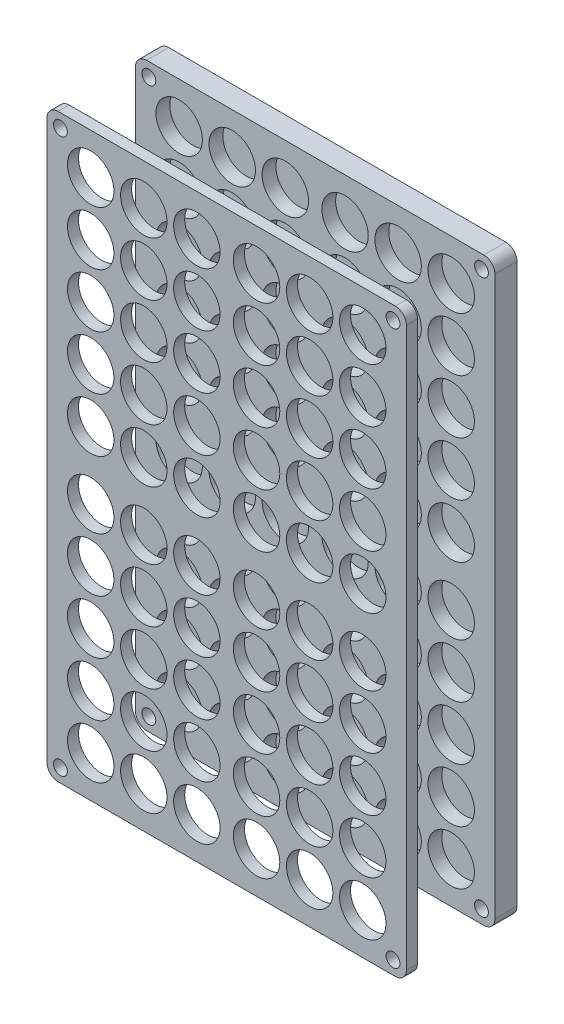
SolidWorks part; units mm, degrees
other "Top Media Holder"
ref_plane "Front Plane" through (0, 0, 0) normal (1, 0, 0) x (0, 1, 0)
ref_plane "Top Plane" through (0, 0, 0) normal (0, 0, 1) x (0, 1, 0)
ref_plane "Right Plane" through (0, 0, 0) normal (0, 1, 0) x (-1, 0, 0)
sketch "Sketch1" plane through (0, 0, 0) normal (0, 0, 1) x (0, 1, 0)
  line L1 (-105, -65) -> (105, -65)
  line L2 (-105, -65) -> (-105, 65)
  line L3 (-105, 65) -> (105, 65)
  line L4 (105, -65) -> (105, 65)
  line L5 (-105, -65) -> (105, 65) construction
  line L6 (-105, 65) -> (105, -65) construction
  point P0 (0, 0)
  dimension "D1" = 130
  dimension "D2" = 210
extrude "120 x 200 x 67 th" add sketch "Sketch1" along normal blind 40
sketch "Sketch2" plane through (0, 0, 40) normal (0, 0, 1) x (1, 0, 0)
  line L0 (-65, 0) -> (65, 0) construction
  line L1 (-65, 105) -> (-65, -105) construction
  line L2 (65, -105) -> (65, 105) construction
  line L3 (0, 105) -> (0, -105) construction
  line L4 (65, 105) -> (-65, 105) construction
  line L5 (-65, -105) -> (65, -105) construction
  line L9 (-65, 40) -> (65, 40) construction
  line L11 (-62.6582, -100.1582) -> (-65, -100.1582)
  line L12 (-60.1582, -102.6582) -> (-60.1582, -105)
  circle A2 centre (-49.2, -12.1416) radius 8.4
  circle A32 centre (-30, -12.1416) radius 8.4
  circle A33 centre (-10.8, -12.1416) radius 8.4
  circle A34 centre (10.8, -12.1416) radius 8.4
  circle A35 centre (30, -12.1416) radius 8.4
  circle A36 centre (49.2, -12.1416) radius 8.4
  circle A37 centre (10.8, -31.6416) radius 8.4
  circle A38 centre (30, -31.6416) radius 8.4
  circle A39 centre (49.2, -31.6416) radius 8.4
  circle A40 centre (-10.8, -31.6416) radius 8.4
  circle A41 centre (-30, -31.6416) radius 8.4
  circle A42 centre (-49.2, -31.6416) radius 8.4
  circle A43 centre (10.8, -51.1416) radius 8.4
  circle A44 centre (30, -51.1416) radius 8.4
  circle A45 centre (49.2, -51.1416) radius 8.4
  circle A46 centre (-10.8, -51.1416) radius 8.4
  circle A47 centre (-30, -51.1416) radius 8.4
  circle A48 centre (-49.2, -51.1416) radius 8.4
  circle A49 centre (10.8, -70.6416) radius 8.4
  circle A50 centre (30, -70.6416) radius 8.4
  circle A51 centre (49.2, -70.6416) radius 8.4
  circle A52 centre (-10.8, -70.6416) radius 8.4
  circle A53 centre (-30, -70.6416) radius 8.4
  circle A54 centre (-49.2, -70.6416) radius 8.4
  circle A55 centre (10.8, -90.1416) radius 8.4
  circle A56 centre (30, -90.1416) radius 8.4
  circle A57 centre (49.2, -90.1416) radius 8.4
  circle A58 centre (-10.8, -90.1416) radius 8.4
  circle A59 centre (-30, -90.1416) radius 8.4
  circle A60 centre (-49.2, -90.1416) radius 8.4
  circle A66 centre (-60.1582, -100.1582) radius 2.5
  circle A67 centre (-60.1582, 100.1582) radius 2.5
  circle A68 centre (60.1582, -100.1582) radius 2.5
  circle A69 centre (60.1582, 100.1582) radius 2.5
  circle A70 centre (-49.2, 90.1416) radius 8.4
  circle A71 centre (-30, 90.1416) radius 8.4
  circle A72 centre (-10.8, 90.1416) radius 8.4
  circle A73 centre (49.2, 90.1416) radius 8.4
  circle A74 centre (30, 90.1416) radius 8.4
  circle A75 centre (10.8, 90.1416) radius 8.4
  circle A76 centre (-49.2, 70.6416) radius 8.4
  circle A77 centre (-30, 70.6416) radius 8.4
  circle A78 centre (-10.8, 70.6416) radius 8.4
  circle A79 centre (49.2, 70.6416) radius 8.4
  circle A80 centre (30, 70.6416) radius 8.4
  circle A81 centre (10.8, 70.6416) radius 8.4
  circle A82 centre (-49.2, 51.1416) radius 8.4
  circle A83 centre (-30, 51.1416) radius 8.4
  circle A84 centre (-10.8, 51.1416) radius 8.4
  circle A85 centre (49.2, 51.1416) radius 8.4
  circle A86 centre (30, 51.1416) radius 8.4
  circle A87 centre (10.8, 51.1416) radius 8.4
  circle A88 centre (-49.2, 31.6416) radius 8.4
  circle A89 centre (-30, 31.6416) radius 8.4
  circle A90 centre (-10.8, 31.6416) radius 8.4
  circle A91 centre (49.2, 31.6416) radius 8.4
  circle A92 centre (30, 31.6416) radius 8.4
  circle A93 centre (10.8, 31.6416) radius 8.4
  circle A94 centre (30, 12.1416) radius 8.4
  circle A95 centre (10.8, 12.1416) radius 8.4
  circle A96 centre (-10.8, 12.1416) radius 8.4
  circle A97 centre (-30, 12.1416) radius 8.4
  circle A98 centre (-49.2, 12.1416) radius 8.4
  circle A99 centre (49.2, 12.1416) radius 8.4
  point P35 (-32.5, 53)
  dimension "D2" = 3
  dimension "D4" = 5
  dimension "D3" = 5
extrude "16.8 D and 52 D tube holes" cut sketch "Sketch2" against normal blind 37 contours A32 | A33 | A34 | A35 | A36 | A42 | A41 | A40 | A37 | A38 | A39 | A48 | A47 | A46 | A43 | A44 | A45 | A54 | A53 | A52 | A49 | A50 | A51 | A60 | A59 | A58 | A55 | A56 | A57 | A71 | A72 | A74 | A73 | A76 | A77 | A78 | A81 | A80 | A79 | A82 | A83 | A84 | A87 | A86 | A85 | A88 | A89 | A90 | A93 | A92 | A91 | A98 | A97 | A96 | A95 | A94 | A99 | A2 | A70 | A75 region at (-49.2, -12.1416, 40) region at (-30, -12.1416, 40) region at (-10.8, -12.1416, 40) region at (10.8, -12.1416, 40) region at (30, -12.1416, 40) region at (49.2, -12.1416, 40) region at (10.8, -31.6416, 40) region at (30, -31.6416, 40) region at (49.2, -31.6416, 40) region at (-10.8, -31.6416, 40) region at (-30, -31.6416, 40) region at (-49.2, -31.6416, 40) region at (10.8, -51.1416, 40) region at (30, -51.1416, 40) region at (49.2, -51.1416, 40) region at (-10.8, -51.1416, 40) region at (-30, -51.1416, 40) region at (-49.2, -51.1416, 40) region at (10.8, -70.6416, 40) region at (30, -70.6416, 40) region at (49.2, -70.6416, 40) region at (-10.8, -70.6416, 40) region at (-30, -70.6416, 40) region at (-49.2, -70.6416, 40) region at (10.8, -90.1416, 40) region at (30, -90.1416, 40) region at (49.2, -90.1416, 40) region at (-10.8, -90.1416, 40) region at (-30, -90.1416, 40) region at (-49.2, -90.1416, 40) region at (-49.2, 90.1416, 40) region at (-30, 90.1416, 40) region at (-10.8, 90.1416, 40) region at (49.2, 90.1416, 40) region at (30, 90.1416, 40) region at (10.8, 90.1416, 40) region at (-49.2, 70.6416, 40) region at (-30, 70.6416, 40) region at (-10.8, 70.6416, 40) region at (49.2, 70.6416, 40) region at (30, 70.6416, 40) region at (10.8, 70.6416, 40) region at (-49.2, 51.1416, 40) region at (-30, 51.1416, 40) region at (-10.8, 51.1416, 40) region at (49.2, 51.1416, 40) region at (30, 51.1416, 40) region at (10.8, 51.1416, 40) region at (-49.2, 31.6416, 40) region at (-30, 31.6416, 40) region at (-10.8, 31.6416, 40) region at (49.2, 31.6416, 40) region at (30, 31.6416, 40) region at (10.8, 31.6416, 40) region at (30, 12.1416, 40) region at (10.8, 12.1416, 40) region at (-10.8, 12.1416, 40) region at (-30, 12.1416, 40) region at (-49.2, 12.1416, 40) region at (49.2, 12.1416, 40)
fillet "4 mm R filet" radius 4 4 edges at (-65, 105, 20) (65, 105, 20) (-65, -105, 20) (65, -105, 20)
sketch "Sketch3" plane through (0, 0, 0) normal (1, 0, 0) x (0, 1, 0)
  line L0 (-105, 0) -> (-105, 8) construction
  line L1 (-105, 40) -> (-105, 36)
  line L2 (-105, 0) -> (-105, 40) construction
  line L3 (105, 40) -> (105, 0) construction
  line L4 (-105, 8) -> (105, 8)
  line L5 (-105, 8) -> (-105, 36)
  line L6 (-105, 36) -> (105, 36)
  line L7 (105, 8) -> (105, 36)
  line L8 (-105, 8) -> (105, 36) construction
  line L9 (-105, 36) -> (105, 8) construction
  point P11 (0, 22)
  dimension "D1" = 8
  dimension "D2" = 4
extrude "Plate Seperating cut" cut sketch "Sketch3" against normal through all both and the other way through all contours L4 L7 L6 L5 region at (0, 0, 22)
extrude "M4 through holes" cut sketch "Sketch2<3>" against normal through all both and the other way through all contours A66 | A68 | A67 | A69 region at (-60.1582, -100.1582, 40) region at (-60.1582, 100.1582, 40) region at (60.1582, -100.1582, 40) region at (60.1582, 100.1582, 40)
sketch "Sketch2<3>" plane through (0, 0, 40) normal (0, 0, 1) x (1, 0, 0) same geometry as "Sketch2"
